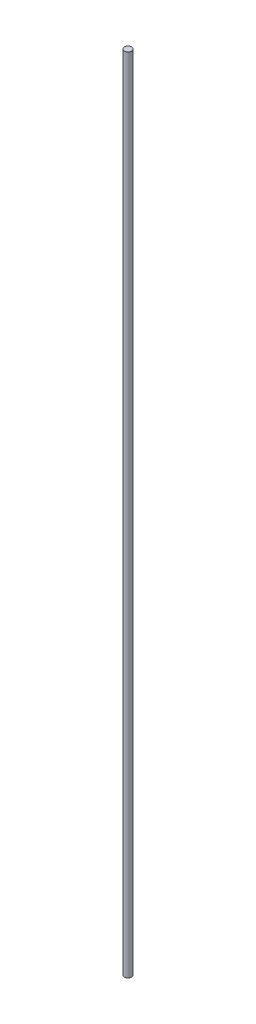
SolidWorks part; units mm, degrees
ref_plane "Спереди" through (0, 0, 0) normal (0, 0, 1) x (1, 0, 0)
ref_plane "Сверху" through (0, 0, 0) normal (0, 1, 0) x (1, 0, 0)
ref_plane "Справа" through (0, 0, 0) normal (1, 0, 0) x (0, 0, -1)
sketch "Эскиз2" plane through (0, 0, 0) normal (0, 0, 1) x (1, 0, 0)
  line L5 (-2.5, 272) -> (0, 272)
  line L6 (-2.5, 272) -> (-2.5, -272)
  line L7 (-2.5, -272) -> (0, -272)
  line L8 (0, 272) -> (0, -272)
  line L9 (-2.5, 272) -> (0, -272) construction
  line L10 (-2.5, -272) -> (0, 272) construction
  point P0 (-1.25, 0)
  point P5 (0, 0)
  dimension "D1" = 2.5
  dimension "D2" = 544
revolve "Повернуть1" add sketch "Эскиз2" angle 360 about L6
equation "\"Ширина груза\"= 420"
equation "\"Глубина груза\"= 490"
equation "\"Высота груза\"= 297"
equation "\"Ширина ячейки\"= \"Ширина груза\" + 10"
equation "\"Глубина ячейки\"= \"Глубина груза\" + 10"
equation "\"Высота ячейки\"= \"Высота груза\" + 10 + 13"
equation "\"Колво ячеек ширина\"= 2"
equation "\"Колво ячеек высота\"= 2"
equation "\"Толщина стенки\" = \"Толщина тонких панелей\""
equation "\"Крепление дверцы\"= 5 "
equation "\"Ширина рейки\"= \"Толщина шестерни\""
equation "\"Высота рейки\"= 20"
equation "\"Высота пола\" = 2*\"Толщина тонких панелей\""
equation "\"Колво полозьев\"= 5"
equation "\"Отступ рейки\"= 20"
equation "\"Глубина каретки\"= \"Глубина ячейки\" + 30 + \"Мотор Y высота корпуса\" + 20"
equation "\"Длинна рейки\" = (\"Ширина ячейки\"+\"Толщина вертикальных стенок\"+\"Крепление дверцы\")*\"Колво ячеек ширина\"+\"Ширина ячейки выгрузки\"*\"Колво выгрузки\"+\"Толщина вертикальных стенок\"+2*\"Отступ крепления мотора фиксации\"-\"Крепление дверцы\"*\"Колво ячеек ширина\""
equation "\"Отступ шпильки\"= 26"
equation "\"Диаметр шпильки\"= 5"
equation "\"Длинна шпильки\" = (\"Высота ячейки\"+\"Толщина горизонтальных плит\"+\"Высота пола\")*\"Колво ячеек высота\"+2*(\"Толщина горизонтальных плит\"+\"Отступ рейки\")"
equation "\"D1@Эскиз2\"= \"Диаметр шпильки\" / 2"
equation "\"D2@Эскиз2\" = \"Глубина каретки\" - \"Мотор Y высота корпуса\" - \"Толщина стенки\""
equation "\"Ширина пластины\"= 50  "
equation "\"Высота зона выгрузки\"= \"Высота ячейки\" * 2 + \"Толщина стенки\" * 2"
equation "\"Колво выгрузки\"= 1"
equation "\"Отступ крепления мотора фиксации\" = (\"Ширина пластины\"+20-\"Толщина вертикальных стенок\")/2"
equation "\"Мотор X ширина корпуса\"= 42.3"
equation "\"Мотор X высота корпуса\"= 42.3"
equation "\"Мотор X длина корпуса\"= 40"
equation "\"Мотор X вылет вала\"= 19.8"
equation "\"Мотор Y ширина корпуса\"= 42.3"
equation "\"Мотор Y высота корпуса\"= 42.3"
equation "\"Мотор Y длина корпуса\"= 48"
equation "\"Мотор Y вылет вала\"= 30"
equation "\"Мотор Z ширина корпуса\"= 42"
equation "\"Мотор Z высота корпуса\"= 42"
equation "\"Мотор Z длина корпуса\"= 40"
equation "\"Мотор Z вылет вала\"= 23"
equation "\"Мотор диаметр вала ПРЕДВ\"= 5"
equation "\"Мотор шаг крепления ПРЕДВ\"= 31"
equation "\"Мотор диаметр отверстий ПРЕДВ\"= 3"
equation "\"Мотор глубина отверстий ПРЕДВ\"= 4.5"
equation "\"Мотор диаметр буртика ПРЕДВ\"= 22"
equation "\"Мотор высота буртика ПРЕДВ\"= 2"
equation "\"Мотор диаметр шкива ПРЕДВ\"= 16"
equation "\"Мотор длина шкива ПРЕДВ\"= 12"
equation "\"Мотор отступ шкива ПРЕДВ\"= 5"
equation "\"Мотор X шаг градусов\"= 1.8"
equation "\"Мотор X ток А\"= 1.5"
equation "\"Мотор X сопротивление Ом\"= 1.3"
equation "\"Мотор X индуктивность мГн\"= 2"
equation "\"Мотор Y шаг градусов\"= 1.8"
equation "\"Мотор Y ток А\"= 2.2"
equation "\"Мотор Y сопротивление Ом\"= 0.9"
equation "\"Мотор Y индуктивность мГн\"= 2"
equation "\"Мотор Z шаг градусов\"= 1.8"
equation "\"Мотор Z ток А\"= 1"
equation "\"Мотор Z сопротивление Ом\"= 4"
equation "\"Мотор Z индуктивность мГн\"= 8"
equation "\"Мотор Y диаметр ротора\"= 25.78"
equation "\"Ширина ячейки выгрузки\" = \"Ширина ячейки\"+\"Толщина вертикальных стенок\"+2*\"Отступ крепления мотора фиксации\""
equation "\"Толщина тонких панелей\"= 6"
equation "\"Толщина вертикальных стенок\"= 18"
equation "\"Толщина горизонтальных плит\"= 18"
equation "\"Базовая высота корпуса\"= (\"Высота ячейки\"+\"Толщина тонких панелей\"+\"Высота пола\")*\"Колво ячеек высота\"+6*\"Толщина тонких панелей\"+\"Мотор X ширина корпуса\"+\"Мотор Y ширина корпуса\"+75"
equation "\"Высота корпуса\"= (\"Высота ячейки\"+\"Толщина горизонтальных плит\"+\"Высота пола\")*\"Колво ячеек высота\"+2*\"Толщина горизонтальных плит\"+4*\"Толщина тонких панелей\"+\"Мотор X ширина корпуса\"+\"Мотор Y ширина корпуса\"+75"
equation "\"Смещение центра корпуса\"= (\"Высота корпуса\"-\"Базовая высота корпуса\")/2-(\"Толщина горизонтальных плит\"-\"Толщина тонких панелей\")"
equation "\"Отметка пола\"= -\"Базовая высота корпуса\"/2+\"Толщина тонких панелей\""
equation "\"Отметка потолка\"= \"Отметка пола\"+\"Высота корпуса\"-2*\"Толщина горизонтальных плит\""
equation "\"Отметка верхней полки\"= \"Отметка потолка\"-(28+\"Толщина тонких панелей\")-\"Высота ячейки\"-\"Высота пола\""
equation "\"Отметка нижней полки\"= \"Отметка верхней полки\"-\"Высота ячейки\"-\"Высота пола\"-\"Толщина горизонтальных плит\""
